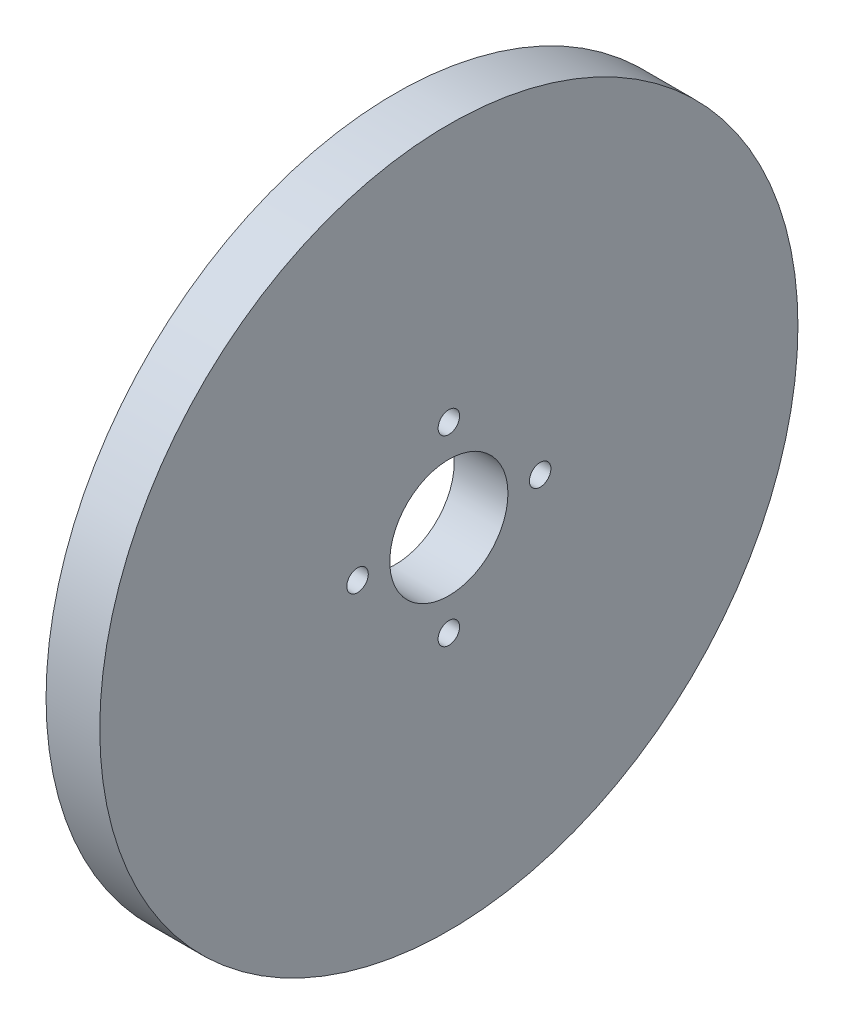
SolidWorks part; units mm, degrees
material "2024-T4"
ref_plane "Front Plane" through (0, 0, 0) normal (0, 0, 1) x (1, 0, 0)
ref_plane "Top Plane" through (0, 0, 0) normal (0, 1, 0) x (1, 0, 0)
ref_plane "Right Plane" through (0, 0, 0) normal (1, 0, 0) x (0, 0, -1)
sketch "Sketch1" plane through (0, 0, 0) normal (1, 0, 0) x (0, 0, -1)
  circle A1 centre (0, 0) radius 65
  dimension "D1" = 130
extrude "Boss-Extrude1" add sketch "Sketch1" along normal mid plane 10
sketch "Sketch3" plane through (5, 0, 0) normal (1, 0, 0) x (0, 0, -1)
  circle A0 centre (0, 0) radius 11
  dimension "D1" = 22
extrude "Cut-Extrude2" cut sketch "Sketch3" against normal through all
sketch "Sketch4" [suppressed] plane through (5, 0, 0) normal (1, 0, 0) x (0, 0, -1)
  circle A0 centre (0, 0) radius 7.5
  dimension "D1" = 15
extrude "Cut-Extrude3" [suppressed] cut sketch "Sketch4" against normal through all
sketch "Sketch5" plane through (5, 0, 0) normal (1, 0, 0) x (0, 0, -1)
  line L0 (0, 0) -> (0, 17) construction
  circle A2 centre (0, 17) radius 2
  circle A3 centre (17, 0) radius 2
  circle A4 centre (0, -17) radius 2
  circle A5 centre (-17, 0) radius 2
  point P12 (0, 0)
  dimension "D2" = 4
  dimension "D1" = 17
  dimension "D4" = 17
  dimension "D5" = 17
  dimension "D3" = 4
sketch "Sketch6" [suppressed] plane through (5, 0, 0) normal (1, 0, 0) x (0, 0, -1)
  line L0 (0, 0) -> (0, 7.5) construction
  line L1 (2, 9.2284) -> (-2, 9.2284)
  line L2 (-2, 9.2284) -> (-2, 7.2284)
  line L3 (2, 9.2284) -> (2, 7.2284)
  circle A0 centre (0, 0) radius 7.5 construction
  arc A1 (2, 7.2284) -> (-2, 7.2284) centre (0, 0) ccw
  point P8 (0, 9.2284)
  dimension "D1" = 4
  dimension "D2" = 2
extrude "Cut-Extrude4" [suppressed] cut sketch "Sketch6" against normal through all contours L1 L2 A1 L3
extrude "Cut-Extrude5" cut sketch "Sketch5" against normal through all contours A2 | A5 | A4 | A3
sketch "Sketch7" [suppressed] plane through (5, 0, 0) normal (1, 0, 0) x (0, 0, -1)
  circle A0 centre (0, 0) radius 8
  dimension "D1" = 16
extrude "Cut-Extrude6" [suppressed] cut sketch "Sketch7" against normal through all
ref_plane "Plane1" [suppressed] through (0, 0, 0) normal (1, 0, 0) x (0, 0, -1)
sketch "Sketch8" [suppressed] plane through (0, 0, 0) normal (1, 0, 0) x (0, 0, -1)
  circle A0 centre (0, 0) radius 6.5
  circle A1 centre (0, 0) radius 8 construction
  circle A2 centre (0, 0) radius 8
  dimension "D1" = 13
extrude "Boss-Extrude2" [suppressed] add sketch "Sketch8" along normal mid plane 1.5
